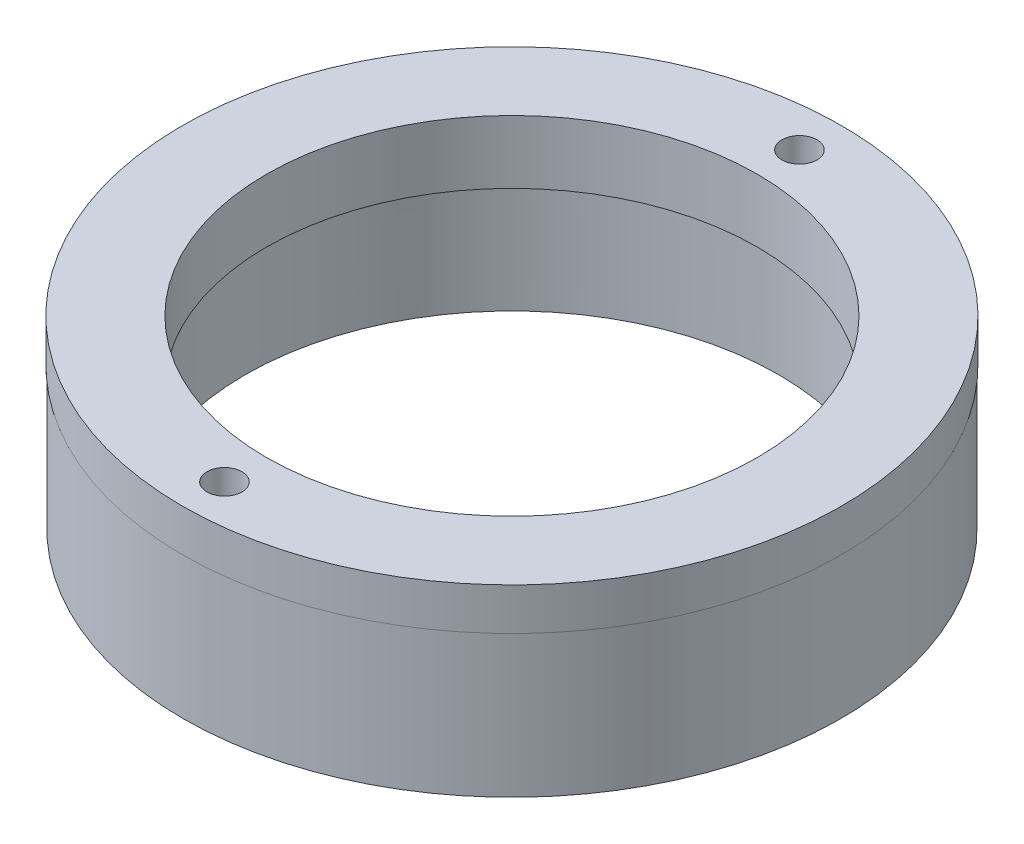
SolidWorks part; units mm, degrees
ref_plane "Plane1" through (0, 0, 0) normal (0, 0, 1) x (1, 0, 0)
ref_plane "Plane2" through (0, 0, 0) normal (0, 1, 0) x (1, 0, 0)
ref_plane "Plane3" through (0, 0, 0) normal (1, 0, 0) x (0, 0, -1)
sketch "Sketch1" plane through (0, 0, 0) normal (0, 1, 0) x (1, 0, 0)
  circle A0 centre (0, 0) radius 11.9126
  dimension "D1" = 23.8252
extrude "Shaft" add sketch "Sketch1" against normal blind 6.6802
ref_plane "Plane4" through (0, 2.54, 0) normal (0, 1, 0) x (-1, 0, 0)
sketch "Sketch5" plane through (0, 2.54, 0) normal (0, 1, 0) x (-1, 0, 0)
  circle A0 centre (0, 0) radius 11.9126 construction
  circle A1 centre (0, 0) radius 11.9126
curve "Helix2" pitch 2.1167 height 10.5833 turns 5
sketch "Sketch6" plane through (0, 0, 0) normal (1, 0, 0) x (0, 0, -1)
  line L0 (-12.0537, 2.4892) -> (-10.5378, 1.614)
  line L1 (-10.5378, 1.614) -> (-10.5378, 1.3494)
  line L2 (-10.5378, 1.3494) -> (-12.0537, 0.4741)
  line L3 (-12.0537, 0.4741) -> (-12.0537, 2.4892)
  line L4 (-10.3086, 1.4817) -> (-13.2352, 1.4817) construction
  line L5 (21.8496, 2.54) -> (-21.8496, 2.54) construction
  point P6 (-11.9126, 0)
  point P10 (-11.9126, 2.4077)
  dimension "D1" = 60
  dimension "D2" = 0.1323
  dimension "D3" = 0.2646
  dimension "D4" = 1.0583
  dimension "D5" = 0.0508
sweep "Thread" [suppressed] cut profiles "Sketch6" path "Helix2"
sketch "Sketch10" plane through (0, 0, 0) normal (1, 0, 0) x (0, 0, -1)
  line L0 (-12.0446, -0.0508) -> (-10.5286, -0.926)
  line L1 (-10.5286, -0.926) -> (-10.5286, -1.1906)
  line L2 (-10.5286, -1.1906) -> (-12.0446, -2.0659)
  line L3 (-12.0446, -2.0659) -> (-12.0446, -0.0508)
  line L4 (-10.2995, -1.0583) -> (-13.2352, -1.0583) construction
  line L5 (0, 0) -> (0, -7.3295) construction
  point P6 (-11.9126, 0)
  point P10 (-11.9126, -0.127)
  dimension "D1" = 60
  dimension "D3" = 0.2646
  dimension "D5" = 1.0583
  dimension "D6" = 0.9313
  dimension "D7" = 0.0762
revolve "Simple Thread" [suppressed] cut sketch "Sketch10" angle 360 about L5
pattern_linear "Pattern Simple Thread" [suppressed] count 4 spacing 2.1167
sketch "Sketch4" plane through (0, 0, 0) normal (0, 1, 0) x (-1, 0, 0)
  circle A0 centre (0, 0) radius 11.938
  dimension "D1" = 23.876
extrude "Cap" add sketch "Sketch4" against normal blind 1.524
sketch "Sketch7" plane through (0, 0, 0) normal (0, 1, 0) x (-1, 0, 0)
  circle A0 centre (0, 0) radius 8.89
  dimension "D1" = 17.78
extrude "Top Hole" cut sketch "Sketch7" against normal blind 2.286
sketch "Sketch8" plane through (0, -2.286, 0) normal (0, 1, 0) x (-1, 0, 0)
  circle A0 centre (0, 0) radius 9.6647
  dimension "D1" = 19.3294
extrude "Bottom Hole" cut sketch "Sketch8" against normal through all
draft "Draft1" type of draft neutral plane draft angle 0.25 faces to draft 1 face at (0, -6.6802, 9.6647) neutral plane through (0, -6.6802, 0) neutral plane normal (0, -1, 0) parameters "D1"=0.25
sketch "Sketch9" plane through (0, 0, 0) normal (0, 1, 0) x (-1, 0, 0)
  line L0 (0, 0) -> (4.0281, 0) construction
  circle A0 centre (0, -10.414) radius 0.635
  circle A1 centre (0, 10.414) radius 0.635
  dimension "D2" = 1.27
  dimension "D1" = 10.414
extrude "Side Holes" cut sketch "Sketch9" against normal blind 1.524
fillet "Fillet1" [suppressed] radius 0.508
